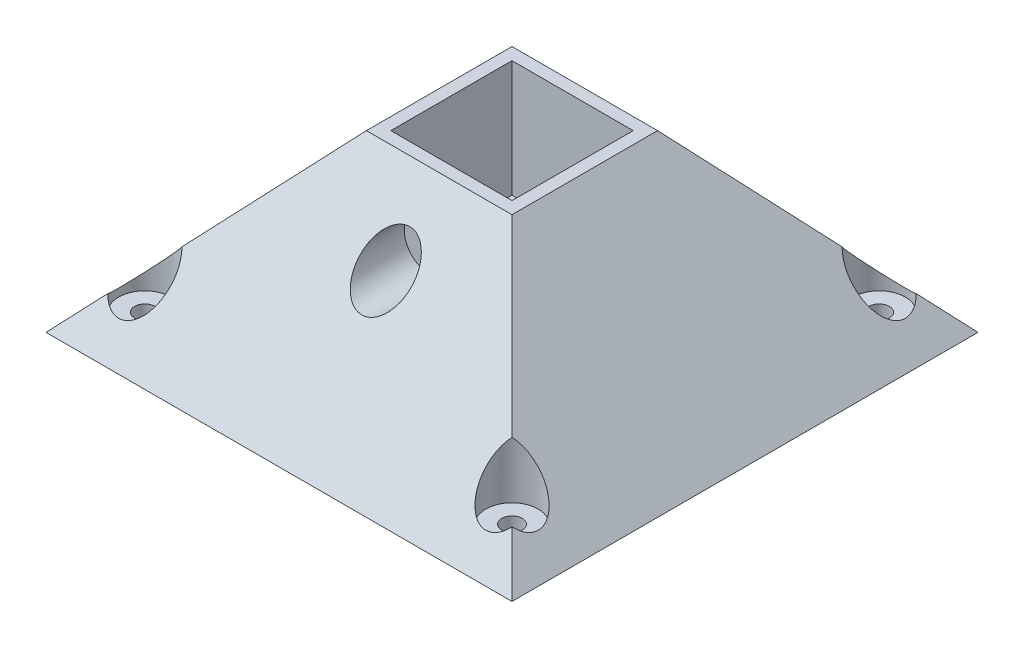
SolidWorks part; units mm, degrees
ref_plane "Front Plane" through (0, 0, 0) normal (0, 0, 1) x (1, 0, 0)
ref_plane "Top Plane" through (0, 0, 0) normal (0, 1, 0) x (1, 0, 0)
ref_plane "Right Plane" through (0, 0, 0) normal (1, 0, 0) x (0, 0, -1)
sketch "Sketch1" plane through (0, 0, 0) normal (0, 1, 0) x (1, 0, 0)
  line L1 (40, -40) -> (-40, -40)
  line L2 (40, -40) -> (40, 40)
  line L3 (40, 40) -> (-40, 40)
  line L4 (-40, -40) -> (-40, 40)
  line L5 (40, -40) -> (-40, 40) construction
  line L6 (40, 40) -> (-40, -40) construction
  point P0 (0, 0)
  point P6 (-30, 23.2697)
  dimension "D1" = 80
ref_plane "Plane1" through (0, 30, 0) normal (0, 1, 0) x (1, 0, 0)
sketch "Sketch2" plane through (0, 30, 0) normal (0, 1, 0) x (1, 0, 0)
  line L1 (12.5, -12.5) -> (-12.5, -12.5)
  line L2 (12.5, -12.5) -> (12.5, 12.5)
  line L3 (12.5, 12.5) -> (-12.5, 12.5)
  line L4 (-12.5, -12.5) -> (-12.5, 12.5)
  line L5 (12.5, -12.5) -> (-12.5, 12.5) construction
  line L6 (12.5, 12.5) -> (-12.5, -12.5) construction
  point P0 (0, 0)
  dimension "D1" = 25
loft "Loft1" add profiles "Sketch2", "Sketch1" connector at (-12.5, 30, 12.5) connector at (-40, 0, 40)
sketch "Sketch3" plane through (0, 30, 0) normal (0, 1, 0) x (1, 0, 0)
  line L0 (40, -40) -> (-40, 40) construction
  line L1 (10.4, -10.4) -> (-10.4, -10.4)
  line L2 (10.4, -10.4) -> (10.4, 10.4)
  line L3 (10.4, 10.4) -> (-10.4, 10.4)
  line L4 (-10.4, -10.4) -> (-10.4, 10.4)
  line L5 (10.4, -10.4) -> (-10.4, 10.4) construction
  line L6 (10.4, 10.4) -> (-10.4, -10.4) construction
  point P0 (0, 0)
  dimension "D1" = 20.8
extrude "Cut-Extrude1" cut sketch "Sketch3" against normal blind 20
sketch "Sketch4" plane through (0, 0, 0) normal (0, 0, 1) x (1, 0, 0)
  line L0 (0, 30) -> (0, 10) construction
  line L1 (44.0001, 30) -> (-44.0001, 30) construction
  line L2 (10.4, 30) -> (-10.4, 30) construction
  line L3 (10.4, 10) -> (-10.4, 10) construction
  circle A0 centre (0, 20) radius 1.75
  circle A1 centre (0, 20) radius 4.5
  dimension "D1" = 3.5
  dimension "D2" = 9
extrude "Cut-Extrude2" cut sketch "Sketch4" along normal through all contours L0 A0 | A0 L0 region at (0.7427, 20, 0) region at (-0.7427, 20, 0)
extrude "Cut-Extrude5" cut sketch "Sketch4<3>" along normal through all from offset 14 contours A1 L0 A0 | L0 A1 A0 region at (2.1178, 20, 0) region at (-2.1178, 20, 0)
sketch "Sketch4<3>" plane through (0, 0, 0) normal (0, 0, 1) x (1, 0, 0) same geometry as "Sketch4"
sketch "Sketch5" plane through (0, 0, 0) normal (0, 1, 0) x (1, 0, 0)
  line L0 (-12.5, 12.5) -> (-40, 40) construction
  circle A0 centre (-31.5147, 31.5147) radius 1.75
  circle A1 centre (-31.5147, 31.5147) radius 4.5
  dimension "D1" = 3.5
  dimension "D2" = 9
  dimension "D3" = 12
extrude "Cut-Extrude6" cut sketch "Sketch5" along normal through all contours A0 region at (-31.5147, 0, -31.5147)
extrude "Cut-Extrude7" cut sketch "Sketch5<3>" along normal through all from offset 3 contours A1 A0 region at (-35.8874, 0, -31.5147)
sketch "Sketch5<3>" plane through (0, 0, 0) normal (0, 1, 0) x (1, 0, 0) same geometry as "Sketch5"
ref_axis "Axis1" through (0, 0, 0) along (0, 1, 0)
pattern_circular "CirPattern1" count 4 over 360 about axis through (0, 0, 0) along (0, 1, 0) of "Cut-Extrude7", "Cut-Extrude6"
